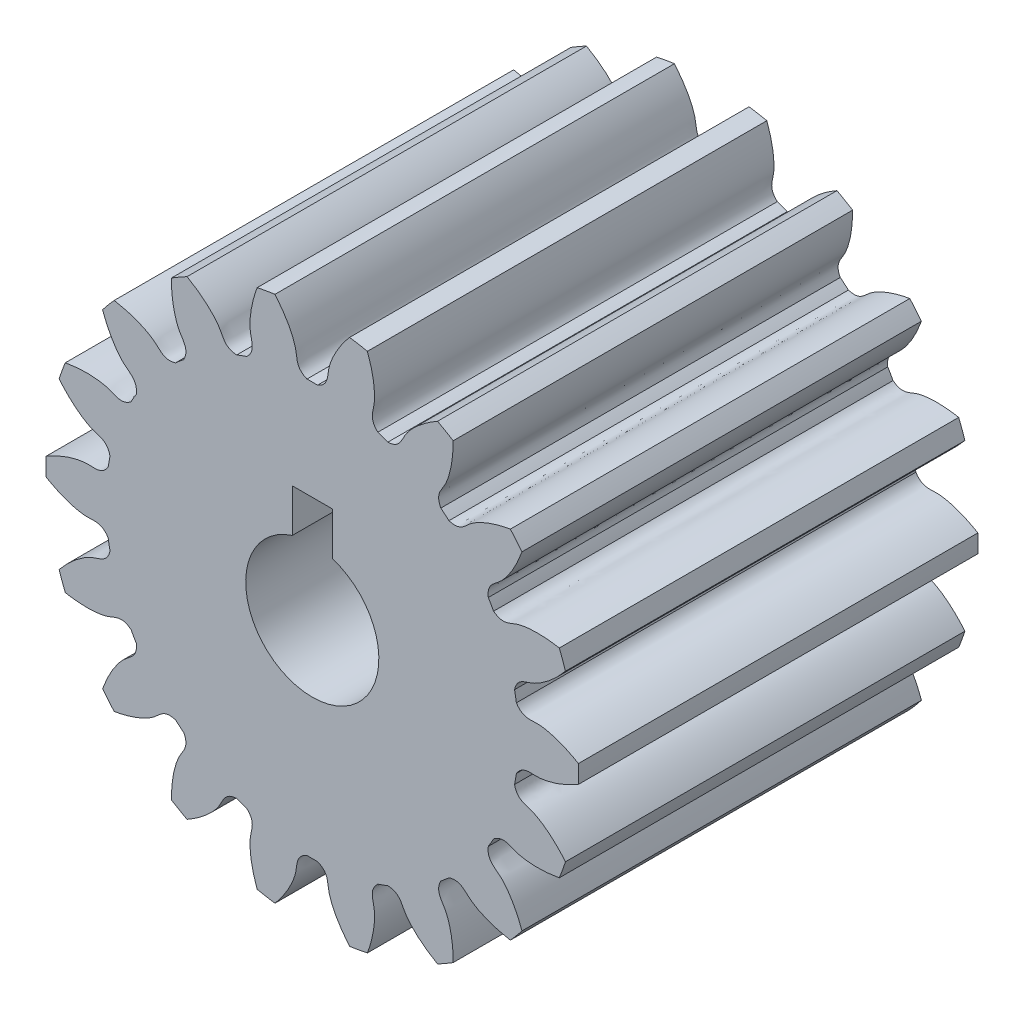
SolidWorks part; units mm, degrees
ref_plane "前视基准面" through (0, 0, 0) normal (0, 0, 1) x (1, 0, 0)
ref_plane "上视基准面" through (0, 0, 0) normal (0, 1, 0) x (1, 0, 0)
ref_plane "右视基准面" through (0, 0, 0) normal (1, 0, 0) x (0, 0, -1)
other "Configuration Table"
sketch "草图1" plane through (0, 0, 0) normal (0, 0, 1) x (1, 0, 0)
  circle A0 centre (0, 0) radius 20
extrude "凸台-拉伸1" add sketch "草图1" along normal blind 30
ref_axis "基准轴1" through (0, 0, -1.5) along (0, 0, 1)
sketch "草图2" plane through (0, 0, 0) normal (0, 0, 1) x (1, 0, 0)
  line L0 (0, 0) -> (0, 20) construction
  circle A0 centre (0, 0) radius 20 construction
  arc A1 (0.3988, 15.4949) -> (-0.3988, 15.4949) centre (0, 0) ccw
  arc A2 (6.1971, 22.6134) -> (-6.1971, 22.6134) centre (0, 0) ccw
  spline S0 degree 3 poles (0.3988, 15.4949) (1.2302, 15.8374) (1.1256, 16.4774) (1.2637, 17.0852) (1.2775, 17.141) (1.2942, 17.2031) (1.314, 17.2713) (1.3373, 17.3456) (1.3641, 17.4258) (1.3948, 17.5118) (1.4296, 17.6035) (1.4688, 17.7008) (1.5126, 17.8035) (1.5611, 17.9115) (1.6148, 18.0246) (1.6737, 18.1427) (1.738, 18.2655) (1.8081, 18.393) (1.8841, 18.5249) (1.9662, 18.6611) (2.0547, 18.8013) (2.1496, 18.9453) (2.2513, 19.0931) (2.3598, 19.2442) (2.4753, 19.3986) (2.5981, 19.5559) (2.7283, 19.7161) (2.866, 19.8787) (3.0115, 20.0437) (3.1648, 20.2106) (3.326, 20.3794) (3.4954, 20.5497) (3.673, 20.7213) (3.859, 20.8939) (4.0534, 21.0673) (4.2564, 21.2412) (4.468, 21.4152) (4.6884, 21.5892) (4.9177, 21.7628) (5.1558, 21.9358) (5.4029, 22.1078) (5.7482, 22.3381) (6.0151, 22.5047) (6.1971, 22.6134) knots 0 0 0 0 0.187592 0.192996 0.199121 0.205966 0.213531 0.221818 0.230824 0.240552 0.250999 0.262168 0.274057 0.286666 0.299996 0.314047 0.328818 0.344309 0.360521 0.377454 0.395107 0.413481 0.432575 0.45239 0.472926 0.494181 0.516158 0.538855 0.562272 0.58641 0.611269 0.636848 0.663148 0.690168 0.717909 0.74637 0.775552 0.805454 0.836077 0.867421 0.899485 0.932269 1 1 1 1
  spline S1 degree 3 poles (-0.3988, 15.4949) (-1.2302, 15.8374) (-1.1256, 16.4774) (-1.2637, 17.0852) (-1.2775, 17.141) (-1.2942, 17.2031) (-1.314, 17.2713) (-1.3373, 17.3456) (-1.3641, 17.4258) (-1.3948, 17.5118) (-1.4296, 17.6035) (-1.4688, 17.7008) (-1.5126, 17.8035) (-1.5611, 17.9115) (-1.6148, 18.0246) (-1.6737, 18.1427) (-1.738, 18.2655) (-1.8081, 18.393) (-1.8841, 18.5249) (-1.9662, 18.6611) (-2.0547, 18.8013) (-2.1496, 18.9453) (-2.2513, 19.0931) (-2.3598, 19.2442) (-2.4753, 19.3986) (-2.5981, 19.5559) (-2.7283, 19.7161) (-2.866, 19.8787) (-3.0115, 20.0437) (-3.1648, 20.2106) (-3.326, 20.3794) (-3.4954, 20.5497) (-3.673, 20.7213) (-3.859, 20.8939) (-4.0534, 21.0673) (-4.2564, 21.2412) (-4.468, 21.4152) (-4.6884, 21.5892) (-4.9177, 21.7628) (-5.1558, 21.9358) (-5.4029, 22.1078) (-5.7482, 22.3381) (-6.0151, 22.5047) (-6.1971, 22.6134) knots 0 0 0 0 0.187592 0.192996 0.199121 0.205966 0.213531 0.221818 0.230824 0.240552 0.250999 0.262168 0.274057 0.286666 0.299996 0.314047 0.328818 0.344309 0.360521 0.377454 0.395107 0.413481 0.432575 0.45239 0.472926 0.494181 0.516158 0.538855 0.562272 0.58641 0.611269 0.636848 0.663148 0.690168 0.717909 0.74637 0.775552 0.805454 0.836077 0.867421 0.899485 0.932269 1 1 1 1
extrude "切除-拉伸1" cut sketch "草图2" along normal through all
pattern_circular "阵列(圆周)1" count 18 every 20 about axis through (0, 0, -1.5) along (0, 0, 1) of "切除-拉伸1"
sketch "草图3" plane through (0, 0, 0) normal (0, 0, 1) x (1, 0, 0)
  circle A0 centre (0, 0) radius 18 construction
  dimension "Dn" = 36
sketch "草图4" plane through (0, 0, 30) normal (0, 0, 1) x (1, 0, 0)
  line L0 (0, 0) -> (-1.5, 0)
  line L1 (-1.5, 0) -> (-1.5, 8)
  line L2 (-1.5, 8) -> (1.5, 8)
  line L3 (1.5, 8) -> (1.5, 0)
  line L4 (1.5, 0) -> (0, 0)
  circle A0 centre (0, 0) radius 5
extrude "切除-拉伸2" cut sketch "草图4" against normal through all contours A0 L3 L2 L1 | L3 A0 L1 L0 L4 | L1 A0 L3 L4 L0 region at (0, -0.5704, 30) region at (0, 2.4625, 30) region at (0, 6.4612, 30)
